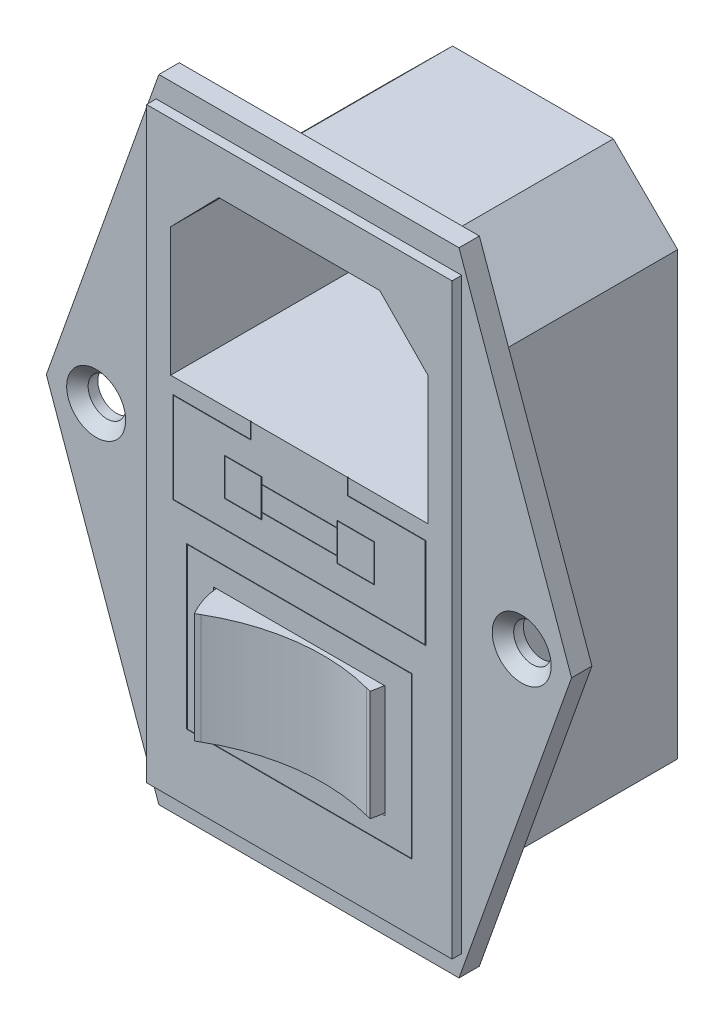
SolidWorks part; units mm, degrees
material "ABS"
ref_plane "Front Plane" through (0, 0, 0) normal (0, 0, 1) x (1, 0, 0)
ref_plane "Top Plane" through (0, 0, 0) normal (0, 1, 0) x (1, 0, 0)
ref_plane "Right Plane" through (0, 0, 0) normal (1, 0, 0) x (0, 0, -1)
sketch "Sketch1" plane through (0, 0, 0) normal (0, 0, 1) x (1, 0, 0)
  line L0 (0, 29.5) -> (0, -29.5) construction
  line L1 (-24.5, 0) -> (24.5, 0) construction
  line L2 (-24.5, 0) -> (-14, 29.5)
  line L3 (-14, 29.5) -> (14, 29.5)
  line L4 (-24.5, 0) -> (-14, -29.5)
  line L5 (-14, -29.5) -> (14, -29.5)
  line L6 (24.5, 0) -> (14, -29.5)
  line L7 (24.5, 0) -> (14, 29.5)
  circle A0 centre (-19.85, 0) radius 1.75
  circle A1 centre (19.85, 0) radius 1.75
  point P10 (0, -29.5)
  point P12 (0, 29.5)
  dimension "D4" = 19.85
  dimension "D5" = 3.5
  dimension "D1" = 29.5
  dimension "D2" = 24.5
  dimension "D3" = 14
extrude "Boss-Extrude1" add sketch "Sketch1" along normal blind 1.9
sketch "Sketch2" plane through (0, 0, 1.9) normal (0, 0, 1) x (1, 0, 0)
  line L1 (-14.25, -27.4) -> (14.25, -27.4)
  line L2 (-14.25, -27.4) -> (-14.25, 27.4)
  line L3 (-14.25, 27.4) -> (14.25, 27.4)
  line L4 (14.25, -27.4) -> (14.25, 27.4)
  line L5 (-14.25, -27.4) -> (14.25, 27.4) construction
  line L6 (-14.25, 27.4) -> (14.25, -27.4) construction
  point P0 (0, 0)
  dimension "D1" = 54.8
  dimension "D2" = 28.5
extrude "Boss-Extrude2" add sketch "Sketch2" along normal blind 0.9
chamfer "Chamfer1" distance 1 angle 45 2 edges at (18.1, 0, 1.9) (-18.1, 0, 1.9)
sketch "Sketch3" plane through (0, 0, 0) normal (0, 0, -1) x (-1, 0, 0)
  line L0 (7.5, 24.6) -> (-7.5, 24.6)
  line L1 (-7.5, 24.6) -> (-13.5, 18.65)
  line L2 (-13.5, 18.65) -> (-13.5, -22.5)
  line L3 (-13.5, -22.5) -> (13.5, -22.5)
  line L4 (0, 29.5) -> (0, -29.5) construction
  line L5 (-14, 29.5) -> (14, 29.5) construction
  line L6 (14, -29.5) -> (-14, -29.5) construction
  line L7 (-24.5, 0) -> (24.5, 0) construction
  line L8 (13.5, 18.65) -> (13.5, -22.5)
  line L9 (7.5, 24.6) -> (13.5, 18.65)
  point P16 (0, -22.5)
  point P18 (0, 24.6)
  dimension "D1" = 13.5
  dimension "D2" = 47.1
  dimension "D3" = 7
  dimension "D4" = 7.5
  dimension "D5" = 5.95
extrude "Boss-Extrude3" add sketch "Sketch3" along normal blind 19
sketch "Sketch4" plane through (0, 0, 2.8) normal (0, 0, 1) x (1, 0, 0)
  line L0 (0, 27.4) -> (0, -27.4) construction
  line L1 (14.25, 27.4) -> (-14.25, 27.4) construction
  line L2 (-14.25, -27.4) -> (14.25, -27.4) construction
  line L3 (7.5, 23.25) -> (-7.5, 23.25)
  line L4 (-7.5, 23.25) -> (-12, 18.65)
  line L5 (-12, 18.65) -> (-12, 6.65)
  line L6 (-12, 6.65) -> (12, 6.65)
  line L7 (12, 18.65) -> (12, 6.65)
  line L8 (7.5, 23.25) -> (12, 18.65)
  point P12 (0, 6.65)
  point P14 (0, 23.25)
  dimension "D1" = 16.6
  dimension "D2" = 4.15
  dimension "D3" = 12
  dimension "D4" = 7.5
  dimension "D5" = 12
extrude "Cut-Extrude1" cut sketch "Sketch4" against normal blind 18.3
sketch "Sketch5" plane through (0, 0, 2.8) normal (0, 0, 1) x (1, 0, 0)
  line L0 (0, 6.65) -> (0, 0) construction
  line L1 (-12, 6.65) -> (12, 6.65) construction
  line L2 (-4.5, 6.65) -> (-4.5, 5.15)
  line L3 (-4.5, 5.15) -> (-11.75, 5.15)
  line L4 (-11.75, 5.15) -> (-11.75, -3.25)
  line L5 (-11.75, -3.25) -> (11.75, -3.25)
  line L6 (11.75, 5.15) -> (11.75, -3.25)
  line L7 (4.5, 5.15) -> (11.75, 5.15)
  line L8 (4.5, 6.65) -> (4.5, 5.15)
  line L9 (-4.55, 6.65) -> (-4.55, 5.2)
  line L10 (-4.55, 5.2) -> (-11.8, 5.2)
  line L11 (-11.8, 5.2) -> (-11.8, -3.3)
  line L12 (-11.8, -3.3) -> (11.8, -3.3)
  line L13 (11.8, 5.2) -> (11.8, -3.3)
  line L14 (4.55, 5.2) -> (11.8, 5.2)
  line L15 (4.55, 6.65) -> (4.55, 5.2)
  line L16 (-4.5, 6.65) -> (-4.55, 6.65)
  line L17 (4.5, 6.65) -> (4.55, 6.65)
  line L18 (0, 2.05) -> (-3.5, 2.05)
  line L19 (-3.5, -0.8) -> (-3.5, 2.7)
  line L20 (-3.5, 2.7) -> (-7, 2.7)
  line L21 (-7, 2.7) -> (-7, -0.8)
  line L22 (0, 2.1) -> (-3.5, 2.1)
  line L23 (-3.5, -0.8) -> (-7, -0.8)
  line L24 (-3.55, -0.75) -> (-3.55, 2.65)
  line L25 (-3.55, 2.65) -> (-6.95, 2.65)
  line L26 (-11.75, 0.95) -> (11.75, 0.95) construction
  line L27 (-6.95, 2.65) -> (-6.95, -0.75)
  line L28 (-3.55, -0.75) -> (-6.95, -0.75)
  line L29 (3.5, -0.15) -> (-3.5, -0.15)
  line L30 (3.5, -0.2) -> (-3.5, -0.2)
  line L31 (3.55, -0.75) -> (6.95, -0.75)
  line L32 (6.95, 2.65) -> (6.95, -0.75)
  line L33 (3.55, 2.65) -> (6.95, 2.65)
  line L34 (3.55, -0.75) -> (3.55, 2.65)
  line L35 (3.5, -0.8) -> (7, -0.8)
  line L36 (0, 2.1) -> (3.5, 2.1)
  line L37 (7, 2.7) -> (7, -0.8)
  line L38 (3.5, 2.7) -> (7, 2.7)
  line L39 (3.5, -0.8) -> (3.5, 2.7)
  line L40 (0, 2.05) -> (3.5, 2.05)
  line L41 (0, 2.05) -> (-3.5, 2.05) construction
  line L42 (0, 2.1) -> (-3.5, 2.1) construction
  line L43 (0, 0) -> (0, -27.4) construction
  line L44 (-14.25, -27.4) -> (14.25, -27.4) construction
  line L45 (-10.45, -6.25) -> (10.45, -6.25)
  line L46 (-10.5, -21.2) -> (10.5, -21.2)
  line L47 (-10.5, -21.2) -> (-10.5, -6.2)
  line L48 (-10.5, -6.2) -> (10.5, -6.2)
  line L49 (10.5, -21.2) -> (10.5, -6.2)
  line L50 (-10.5, -21.2) -> (10.5, -6.2) construction
  line L51 (-10.5, -6.2) -> (10.5, -21.2) construction
  line L52 (10.45, -21.15) -> (10.45, -6.25)
  line L53 (-10.45, -21.15) -> (10.45, -21.15)
  line L54 (-10.45, -21.15) -> (-10.45, -6.25)
  line L56 (-8, -18.95) -> (8, -18.95)
  line L57 (-8, -18.95) -> (-8, -8.45)
  line L58 (-8, -8.45) -> (8, -8.45)
  line L59 (8, -18.95) -> (8, -8.45)
  line L60 (-8, -18.95) -> (8, -8.45) construction
  line L61 (-8, -8.45) -> (8, -18.95) construction
  point P11 (0, -3.25)
  point P22 (3.5, 0.95)
  point P33 (-7, 0.95)
  point P34 (-3.5, 0.95)
  point P43 (0, -0.2)
  point P44 (0, -0.15)
  point P55 (7, 0.95)
  point P56 (0, -13.7)
  point P70 (0, -13.7)
  dimension "D1" = 1.5
  dimension "D2" = 4.5
  dimension "D3" = 11.75
  dimension "D4" = 8.4
  dimension "D6" = 7
  dimension "D7" = 3.5
  dimension "D8" = 1.75
  dimension "D9" = 1.1
  dimension "D12" = 21
  dimension "D13" = 15
  dimension "D14" = 6.2
  dimension "D16" = 16
  dimension "D17" = 10.5
  dimension "D5" = 0.05
  dimension "D10" = 0.05
  dimension "D11" = 0.05
  dimension "D15" = 0.05
extrude "Cut-Extrude2" cut sketch "Sketch5" against normal blind 0.05 contours L23 L19 L20 L21 L24 L28 L27 L25 | L18 L40 L39 L36 L22 L19 | L30 L39 L29 L19 | L39 L35 L37 L38 L31 L34 L33 L32 | L46 L49 L48 L47 L53 L54 L45 L52 | L2 L3 L4 L5 L6 L7 L8 L17 L15 L14 L13 L12 L11 L10 L9 L16 region at (0, 2.075, 2.8) region at (-3.5495, 0.95, 2.8) region at (3.5495, 2.075, 2.8) region at (0, -0.175, 2.8) region at (-10.4742, -13.7, 2.8)
sketch "Sketch6" plane through (0, 0, -19) normal (0, 0, -1) x (-1, 0, 0)
  line L0 (0, 24.6) -> (0, -22.5) construction
  line L1 (7.5, 24.6) -> (-7.5, 24.6) construction
  line L2 (-13.5, -22.5) -> (13.5, -22.5) construction
  line L4 (-12, -21.25) -> (12, -21.25)
  line L5 (-12, -21.25) -> (-12, -5.75)
  line L6 (-12, -5.75) -> (12, -5.75)
  line L7 (12, -21.25) -> (12, -5.75)
  line L8 (-12, -21.25) -> (12, -5.75) construction
  line L9 (-12, -5.75) -> (12, -21.25) construction
  point P6 (0, -13.5)
  dimension "D1" = 24
  dimension "D2" = 15.5
  dimension "D3" = 1.25
extrude "Cut-Extrude3" cut sketch "Sketch6" against normal up to surface (19 mm away) up to face at (18.1, 0, 0)
sketch "Sketch7" plane through (0, -22.5, 0) normal (0, -1, 0) x (1, 0, 0)
  line L0 (8.5, -19) -> (4.4585, -12)
  line L1 (13.5, -19) -> (-13.5, -19) construction
  line L2 (4.4585, -12) -> (-4.4585, -12)
  line L3 (8.5, -19) -> (-8.5, -19)
  line L4 (0, -19) -> (0, -12) construction
  line L5 (-8.5, -19) -> (-4.4585, -12)
  dimension "D1" = 7
  dimension "D2" = 120
  dimension "D3" = 8.5
extrude "Cut-Extrude4" cut sketch "Sketch7" against normal up to surface (1.25 mm away) up to face at (0, -21.25, -9.5)
sketch "Sketch8" plane through (0, 0, 0) normal (0, 0, -1) x (-1, 0, 0)
  line L0 (0, -5.75) -> (0, -21.25) construction
  line L1 (12, -5.75) -> (-12, -5.75) construction
  line L2 (-12, -21.25) -> (12, -21.25) construction
  line L4 (-10, -20) -> (10, -20)
  line L5 (-10, -20) -> (-10, -7)
  line L6 (-10, -7) -> (10, -7)
  line L7 (10, -20) -> (10, -7)
  line L8 (-10, -20) -> (10, -7) construction
  line L9 (-10, -7) -> (10, -20) construction
  point P6 (0, -13.5)
  dimension "D1" = 20
  dimension "D2" = 13
extrude "Boss-Extrude4" add sketch "Sketch8" along normal blind 14
extrude "Cut-Extrude6" cut sketch "Sketch5<3>" against normal blind 1 contours L56 L59 L58 L57 region at (0, -13.7, 2.8)
sketch "Sketch5<3>" plane through (0, 0, 2.8) normal (0, 0, 1) x (1, 0, 0) same geometry as "Sketch5"
sketch "Sketch10" plane through (0, 0, 1.8) normal (0, 0, 1) x (1, 0, 0)
  line L0 (0, -8.45) -> (0, -18.95)
  line L1 (-8, -8.45) -> (8, -8.45) construction
  line L2 (-8, -18.95) -> (8, -18.95) construction
  line L3 (8, -18.95) -> (8, -8.45) construction
  line L4 (-7.9, -18.85) -> (7.9, -18.85)
  line L5 (-7.9, -18.85) -> (-7.9, -8.55)
  line L6 (-7.9, -8.55) -> (7.9, -8.55)
  line L7 (7.9, -18.85) -> (7.9, -8.55)
  line L8 (-7.9, -18.85) -> (7.9, -8.55) construction
  line L9 (-7.9, -8.55) -> (7.9, -18.85) construction
  point P6 (0, -13.7)
  dimension "D1" = 0.1
  dimension "D2" = 0.1
revolve "Revolve2" add sketch "Sketch10" angle 30 about L0 region at (-3.95, -13.7, 1.8) reverse direction yes
revolve "Revolve3" add sketch "Sketch10<6>" angle 15 about L0 region at (3.95, -13.7, 1.8)
sketch "Sketch10<6>" plane through (0, 0, 1.8) normal (0, 0, 1) x (1, 0, 0) same geometry as "Sketch10"
fillet "Fillet1" radius 18 1 edges at (0, -13.7, 1.8)
